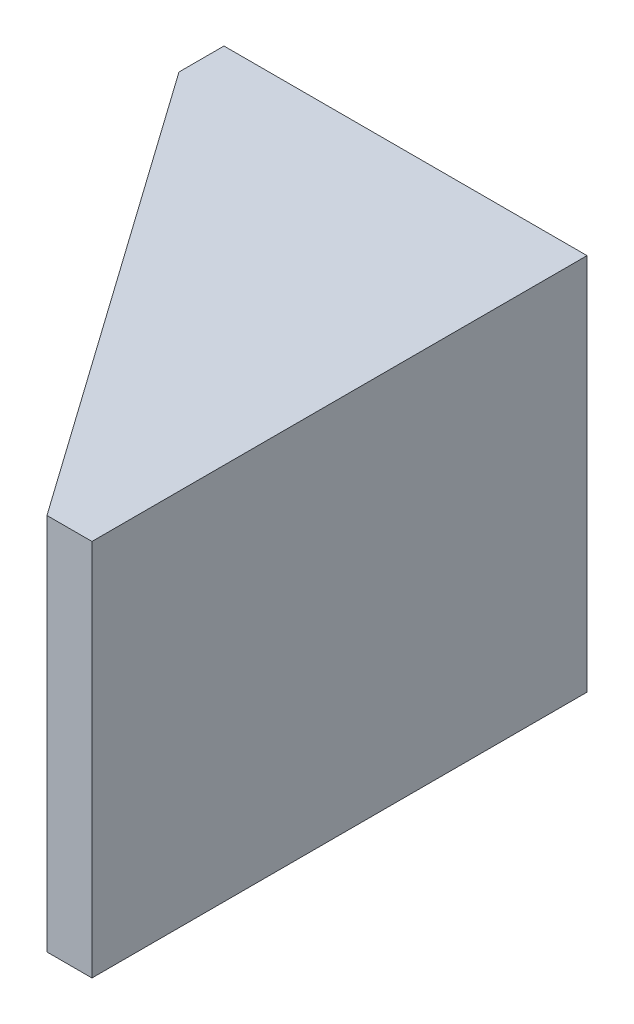
SolidWorks part; units mm, degrees
ref_plane "Front Plane" through (0, 0, 0) normal (0, 0, 1) x (1, 0, 0)
ref_plane "Top Plane" through (0, 0, 0) normal (0, 1, 0) x (1, 0, 0)
ref_plane "Right Plane" through (0, 0, 0) normal (1, 0, 0) x (0, 0, -1)
sketch "Sketch2" plane through (0, 0, 0) normal (0, 1, 0) x (1, 0, 0)
  line L0 (-42.4, 0) -> (0, 0)
  line L1 (0, 0) -> (0, -60)
  line L2 (-42.4, 0) -> (-42.4, 6)
  line L3 (-42.4, 6) -> (6, 6)
  line L4 (6, 6) -> (6, -60)
  line L5 (6, -60) -> (0, -60)
  dimension "D1" = 42.4
  dimension "D2" = 60
  dimension "D3" = 6
  dimension "D4" = 6
extrude "Boss-Extrude1" add sketch "Sketch2" along normal blind 50.4
sketch "Sketch3" plane through (0, 0, 0) normal (0, 0, 1) x (1, 0, 0)
  line L0 (-42.4, 50.4) -> (0, 0) construction
  line L2 (-36.7, 9.7) -> (-5.7, 9.7) construction
  line L3 (-36.7, 9.7) -> (-36.7, 40.7) construction
  line L4 (-36.7, 40.7) -> (-5.7, 40.7) construction
  line L5 (-5.7, 9.7) -> (-5.7, 40.7) construction
  line L6 (-36.7, 9.7) -> (-5.7, 40.7) construction
  line L7 (-36.7, 40.7) -> (-5.7, 9.7) construction
  circle A0 centre (-21.2, 25.2) radius 11.5
  circle A1 centre (-36.7, 40.7) radius 1.5
  circle A2 centre (-5.7, 40.7) radius 1.5
  circle A3 centre (-5.7, 9.7) radius 1.5
  circle A4 centre (-36.7, 9.7) radius 1.5
  dimension "D1" = 23
  dimension "D2" = 3
  dimension "D3" = 31
extrude "Cut-Extrude1" cut sketch "Sketch3" against normal through all
sketch "Sketch4" plane through (0, 50.4, 0) normal (0, 1, 0) x (1, 0, 0)
  line L0 (-42.4, 6) -> (6, 6)
  line L1 (6, 6) -> (6, -60)
  line L2 (6, -60) -> (0, -60)
  line L3 (0, -60) -> (-42.4, 0)
  line L4 (-42.4, 0) -> (-42.4, 6)
extrude "Boss-Extrude2" add sketch "Sketch4" against normal blind 4 contours L3 L4 L0 L1 L2
ref_plane "Plane1" through (0, 25.2, 0) normal (0, 1, 0) x (1, 0, 0)
mirror "Mirror1" about plane through (0, 25.2, 0) normal (0, 1, 0) of "Boss-Extrude2"
